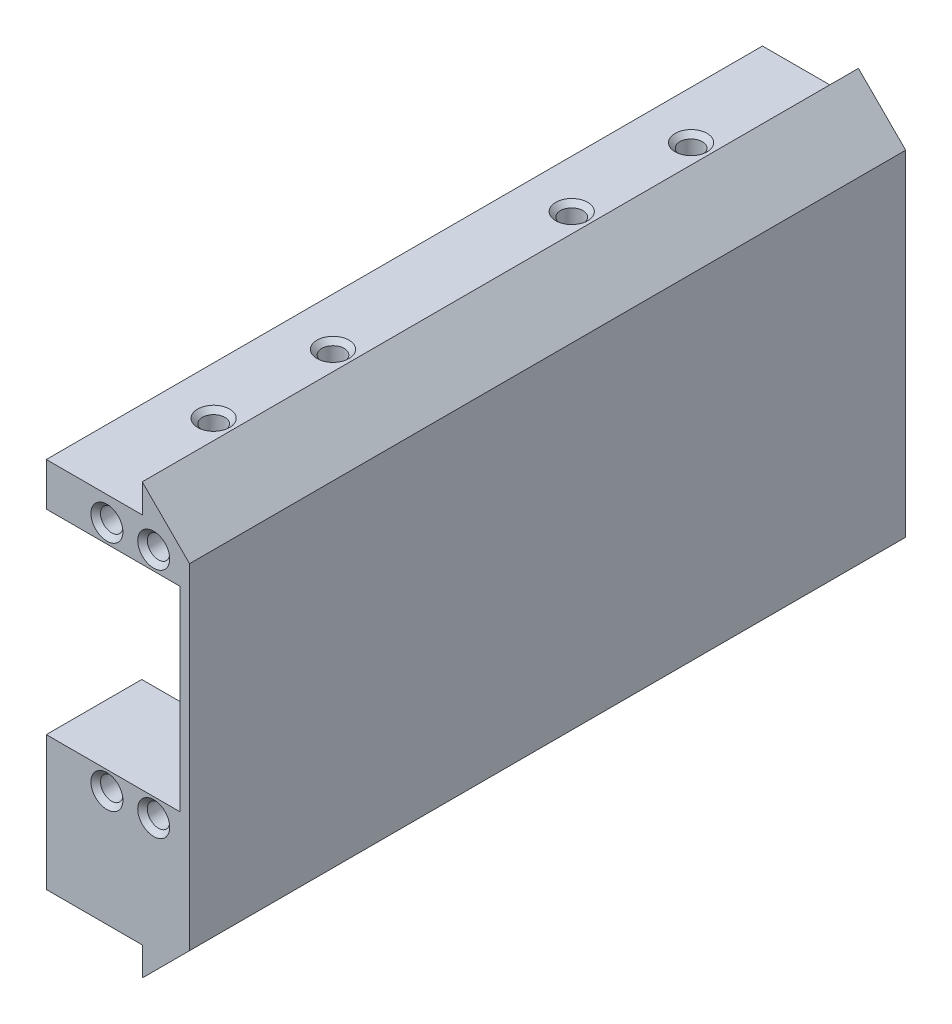
SolidWorks part; units mm, degrees
material "ABS"
ref_plane "Front Plane" through (0, 0, 0) normal (0, 0, 1) x (1, 0, 0)
ref_plane "Top Plane" through (0, 0, 0) normal (0, 1, 0) x (1, 0, 0)
ref_plane "Right Plane" through (0, 0, 0) normal (1, 0, 0) x (0, 0, -1)
sketch "Sketch1" plane through (0, 0, 0) normal (0, 0, 1) x (1, 0, 0)
  line L0 (-15, 45) -> (15, 45)
  line L1 (-15, 45) -> (15, 45) construction
  line L2 (-15, 45) -> (-15, -45) construction
  line L3 (-15, -45) -> (15, -45) construction
  line L4 (15, 45) -> (15, -45) construction
  line L5 (-15, 45) -> (15, -45) construction
  line L6 (-15, -45) -> (15, 45) construction
  line L7 (15, 45) -> (15, -45)
  line L8 (15, -45) -> (-15, -45)
  line L9 (-15, -45) -> (-15, -10.9)
  line L10 (-15, -10.9) -> (13, -10.9)
  line L11 (13, -10.9) -> (13, 30)
  line L12 (13, 30) -> (-15, 30)
  line L13 (-15, 30) -> (-15, 45)
  point P0 (0, 0)
  dimension "D1" = 90
  dimension "D2" = 30
  dimension "D3" = 40.9
  dimension "D4" = 15
  dimension "D5" = 2
extrude "Boss-Extrude1" add sketch "Sketch1" along normal blind 150
sketch "Sketch2" plane through (0, 0, 150) normal (0, 0, 1) x (1, 0, 0)
  line L0 (13, 30) -> (-7.8, 30) construction
  line L1 (-15, 30) -> (13, 30) construction
  line L2 (2.6, 30) -> (2.6, 33.89) construction
  line L3 (2.6, 33.89) -> (7.5, 33.89) construction
  line L4 (13, 30) -> (13, -10.9) construction
  line L5 (13, 9.55) -> (15, 9.55) construction
  line L7 (15, -45) -> (15, 45) construction
  circle A0 centre (7.5, 33.89) radius 2.35
  circle A1 centre (-2.3, 33.89) radius 2.35
  circle A4 centre (7.5, -14.79) radius 2.35
  circle A5 centre (-2.3, -14.79) radius 2.35
  dimension "D4" = 4.7
  dimension "D1" = 20.8
  dimension "D2" = 3.89
  dimension "D3" = 4.9
extrude "Cut-Extrude1" cut sketch "Sketch2" against normal blind 8
sketch "Sketch3" plane through (0, 0, 0) normal (0, 0, -1) x (-1, 0, 0)
  line L0 (-13, 30) -> (7.8, 30) construction
  line L1 (15, 30) -> (-13, 30) construction
  line L2 (-13, 30) -> (-13, -10.9) construction
  line L3 (-13, 9.55) -> (-15, 9.55) construction
  line L5 (-2.6, 30) -> (-2.6, 33.89) construction
  line L6 (-2.6, 33.89) -> (-7.5, 33.89) construction
  line L7 (-15, -45) -> (-15, 45) construction
  circle A0 centre (-7.5, 33.89) radius 2.35
  circle A1 centre (2.3, 33.89) radius 2.35
  circle A4 centre (-7.5, -14.79) radius 2.35
  circle A5 centre (2.3, -14.79) radius 2.35
  dimension "D4" = 4.7
  dimension "D1" = 20.8
  dimension "D2" = 3.89
  dimension "D3" = 4.9
extrude "Cut-Extrude2" cut sketch "Sketch3" against normal blind 8
chamfer "Chamfer1" distance 1 angle 45 8 edges at (5.15, 33.89, 0) (0.05, 33.89, 0) (-4.65, 33.89, 150) (9.85, 33.89, 150) (5.15, -14.79, 150) (0.05, -14.79, 150) (-4.65, -14.79, 0) (9.85, -14.79, 0)
sketch "Sketch4" plane through (0, 0, 150) normal (0, 0, 1) x (1, 0, 0)
  line L0 (0, 0) -> (15, 0) construction
  line L1 (-15, -45) -> (5.1, -45)
  line L2 (-15, -45) -> (-15, -39)
  line L3 (-15, -39) -> (5.1, -39)
  line L4 (5.1, -45) -> (5.1, -39)
  line L5 (15, -45) -> (15, 45) construction
  line L6 (-15, 39) -> (5.1, 39)
  line L7 (5.1, 45) -> (5.1, 39)
  line L8 (-15, 45) -> (5.1, 45)
  line L9 (-15, 45) -> (-15, 39)
  dimension "D1" = 6
  dimension "D2" = 20.1
extrude "Cut-Extrude3" cut sketch "Sketch4" against normal through all
chamfer "Chamfer2" distance 9.9 angle 45 2 edges at (15, -45, 75) (15, 45, 75)
sketch "Sketch5" plane through (0, 39, 0) normal (0, 1, 0) x (1, 0, 0)
  line L0 (-4.95, 0) -> (-4.95, -25) construction
  line L1 (-15, 0) -> (5.1, 0) construction
  line L2 (-4.95, -25) -> (-4.95, -50) construction
  line L3 (-4.95, -50) -> (-4.95, -75) construction
  line L4 (-4.95, -100) -> (-4.95, -125) construction
  line L5 (-4.95, -125) -> (-4.95, -150) construction
  line L6 (-15, -150) -> (5.1, -150) construction
  line L8 (-4.95, -75) -> (-4.95, -100) construction
  line L10 (5.1, 0) -> (-15, 0) construction
  line L11 (5.1, 0) -> (5.1, -150) construction
  line L12 (5.1, -150) -> (-15, -150) construction
  line L13 (-15, 0) -> (-15, -150) construction
  circle A0 centre (-4.95, -25) radius 2.35
  circle A1 centre (-4.95, -50) radius 2.35
  circle A2 centre (-4.95, -100) radius 2.35
  circle A3 centre (-4.95, -125) radius 2.35
  dimension "D1" = 4.7
  dimension "D2" = 4.7
  dimension "D3" = 4.7
  dimension "D4" = 4.7
  dimension "D5" = 20.1
  dimension "D6" = 150
extrude "Cut-Extrude4" cut sketch "Sketch5" against normal blind 8
chamfer "Chamfer3" distance 1 angle 45 4 edges at (-4.95, 39, 127.35) (-4.95, 39, 102.35) (-4.95, 39, 52.35) (-4.95, 39, 27.35)
sketch "Sketch6" plane through (0, -39, 0) normal (0, -1, 0) x (1, 0, 0)
  line L1 (5, 121) -> (-15, 121) construction
  line L2 (5, 121) -> (5, 29) construction
  line L3 (5, 29) -> (-15, 29) construction
  line L4 (-15, 121) -> (-15, 29) construction
  line L5 (-15, 0) -> (-15, 150) construction
  line L6 (5.1, 150) -> (-15, 150) construction
  line L7 (5.1, 0) -> (-15, 0) construction
  line L8 (-5, 121) -> (-5, 90.3333) construction
  line L9 (-5, 90.3333) -> (-5, 59.6667) construction
  line L10 (-5, 59.6667) -> (-5, 29) construction
  circle A0 centre (-5, 59.6667) radius 6.1
  circle A1 centre (-5, 90.3333) radius 6.1
  dimension "D3" = 12.2
  dimension "D4" = 12.2
  dimension "D1" = 29
  dimension "D2" = 29
  dimension "D5" = 10
  dimension "D6" = 10
  dimension "D7" = 20
extrude "Cut-Extrude5" cut sketch "Sketch6" against normal blind 3.2
sketch "Sketch8" plane through (-15, 0, 0) normal (-1, 0, 0) x (0, 0, 1)
  line L0 (150, -10.9) -> (130, -10.9) construction
  line L1 (150, -10.9) -> (0, -10.9) construction
  line L2 (0, -10.9) -> (20, -10.9) construction
  line L3 (150, -10.9) -> (0, -10.9) construction
  line L5 (20, -10.9) -> (130, -10.9)
  line L6 (20, -10.9) -> (20, -32.8)
  line L7 (20, -32.8) -> (130, -32.8)
  line L8 (130, -10.9) -> (130, -32.8)
  line L9 (53.5667, -35.8) -> (65.7667, -35.8) construction
  dimension "D1" = 20
  dimension "D2" = 20
  dimension "D3" = 3
extrude "Cut-Extrude7" cut sketch "Sketch8" against normal up to surface (28 mm away) up to face at (13, 9.55, 75)
fillet "Fillet1" radius 0.2 2 edges at (-5, -39, 84.2333) (-5, -39, 53.5667)
sketch "Sketch9" plane through (13, 0, 0) normal (-1, 0, 0) x (0, 0, 1)
  line L0 (150, 30) -> (0, 30) construction
  line L1 (35, 30) -> (115, 30)
  line L2 (35, 30) -> (35, -32.8)
  line L3 (35, -32.8) -> (115, -32.8)
  line L4 (115, 30) -> (115, -32.8)
  line L5 (20, -32.8) -> (130, -32.8) construction
  line L6 (20, -10.9) -> (20, -32.8) construction
  line L7 (130, -32.8) -> (130, -10.9) construction
  dimension "D1" = 15
  dimension "D2" = 15
extrude "Boss-Extrude2" add sketch "Sketch9" along normal blind 3
